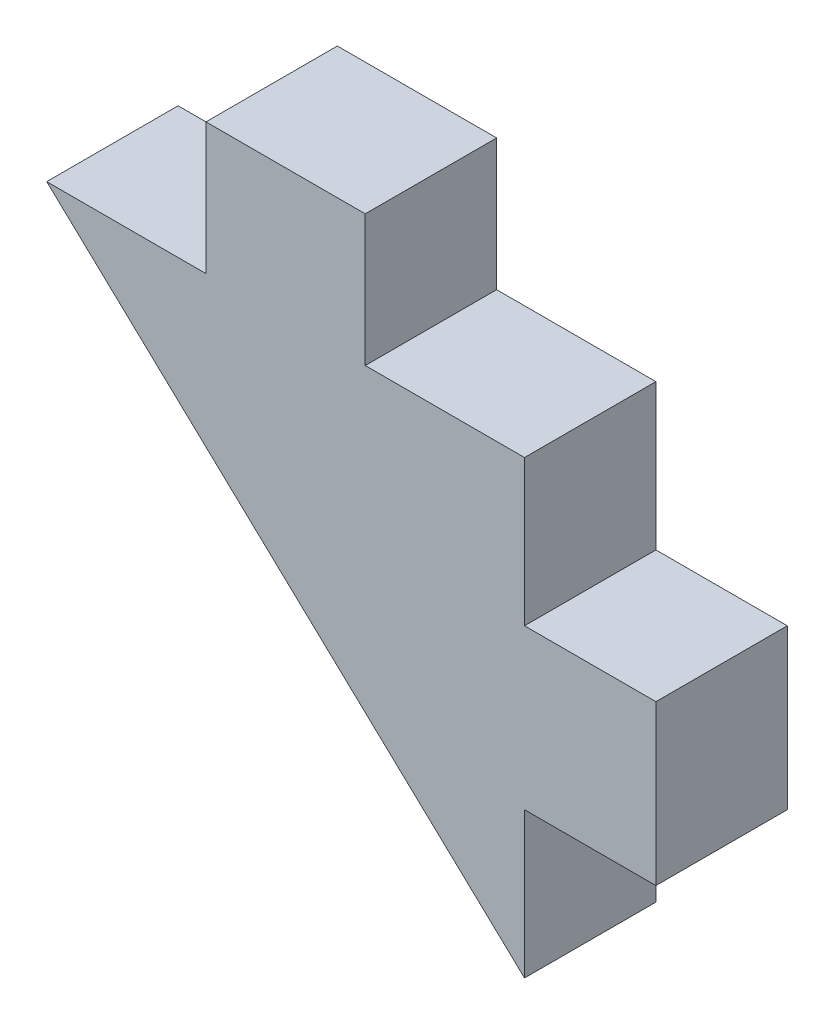
SolidWorks part; units mm, degrees
ref_plane "Front Plane" through (0, 0, 0) normal (0, 0, 1) x (1, 0, 0)
ref_plane "Top Plane" through (0, 0, 0) normal (0, 1, 0) x (1, 0, 0)
ref_plane "Right Plane" through (0, 0, 0) normal (1, 0, 0) x (0, 0, -1)
sketch "Sketch1" plane through (0, 0, 0) normal (0, 0, 1) x (1, 0, 0)
  line L0 (-10, 9.434) -> (10, -9.434)
  line L1 (3.3333, 9.434) -> (10, 9.434)
  line L2 (10, 3.3333) -> (10, 9.434)
  line L3 (-10, 9.434) -> (-3.3333, 9.434)
  line L4 (10, -9.434) -> (10, -3.3333)
  line L5 (0, 0) -> (10, 9.434) construction
  line L6 (-10, 9.434) -> (10, -9.434) construction
  line L8 (-3.3333, 9.434) -> (-3.3333, 14.934)
  line L9 (-3.3333, 14.934) -> (3.3333, 14.934)
  line L10 (3.3333, 9.434) -> (3.3333, 14.934)
  line L11 (0, 10.8346) -> (3.3333, 14.934) construction
  line L12 (-3.3333, 14.934) -> (0, 10.8346) construction
  line L13 (10, -3.3333) -> (15.5, -3.3333)
  line L15 (10, 3.3333) -> (15.5, 3.3333)
  line L16 (15.5, -3.3333) -> (15.5, 3.3333)
  line L17 (10, 0) -> (15.5, 3.3333) construction
  line L18 (10, 0) -> (15.5, -3.3333) construction
  point P0 (0, 0)
  point P6 (0, 10.8346)
  point P11 (10, 0)
  dimension "D1" = 5.5
  dimension "D2" = 6.6667
  dimension "D3" = 6.6667
  dimension "D4" = 5.5
extrude "Boss-Extrude1" add sketch "Sketch1" along normal blind 5.5
equation "\"D1@Boss-Extrude1\" = \"mat@v1.assembly\""
equation "\"D4@Sketch1\" = \"mat@V1.assembly\""
equation "\"D1@Sketch1\"=\"mat@V1.assembly\""
